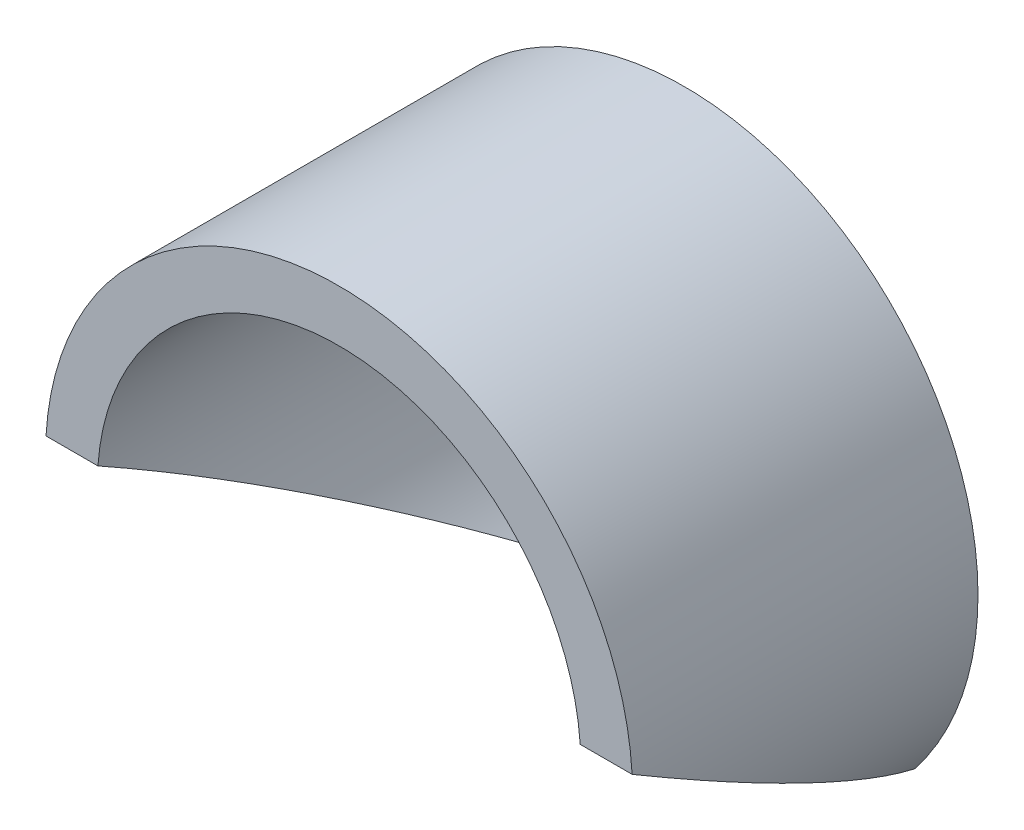
SolidWorks part; units mm, degrees
note: The reader was unsure of these and kept them because the rebuilt part matched: shared geometry of "Sketch23<2>".
ref_plane "Front Plane" through (0, 0, 0) normal (0, 0, 1) x (1, 0, 0)
ref_plane "Top Plane" through (0, 0, 0) normal (0, 1, 0) x (1, 0, 0)
ref_plane "Right Plane" through (0, 0, 0) normal (1, 0, 0) x (0, 0, -1)
sketch "Sketch1" plane through (0, 0, 0) normal (0, 1, 0) x (1, 0, 0)
  line L1 (0, 0) -> (121, 0)
  line L2 (0, 0) -> (0, -68)
  line L3 (0, -68) -> (121, -68)
  line L4 (121, 0) -> (121, -68)
  line L5 (5, -68) -> (116, -68)
  line L6 (5, -68) -> (5, -5)
  line L7 (5, -5) -> (116, -5)
  line L8 (116, -68) -> (116, -5)
  dimension "D1" = 121
  dimension "D2" = 68
  dimension "D3" = 5
  dimension "D4" = 5
  dimension "D5" = 5
extrude "Boss-Extrude1" add sketch "Sketch1" along normal blind 5 contours L8 L3 L4 L1 L2 L6 L7
ref_plane "Plane1" through (0, 3.75, 2.1651) normal (0, 0.866, 0.5) x (1, 0, 0)
sketch "Sketch2" plane through (0, 3.75, 2.1651) normal (0, 0.866, 0.5) x (1, 0, 0)
  line L2 (121, 2.5) -> (121, -56.3897) construction
  line L3 (0, 2.5) -> (121, 2.5) construction
  circle A0 centre (118.2001, -0.2999) radius 2.5
  dimension "D1" = 5
  dimension "D2" = 2.7999
  dimension "D3" = 2.7999
extrude "Boss-Extrude2" add sketch "Sketch2" along normal blind 100
ref_plane "Plane2" through (0, 0, 68) normal (0, 0, 1) x (1, 0, 0)
sketch "Sketch3" plane through (121, 0, 0) normal (1, 0, 0) x (0, 0, -1)
  line L0 (0, 5) -> (-68, 5) construction
  line L1 (0, 0) -> (-5, 0)
  line L2 (0, 0) -> (0, 5)
  line L3 (0, 5) -> (-5, 5)
  line L4 (-5, 0) -> (-5, 5)
  dimension "D1" = 5
extrude "Boss-Extrude3" add sketch "Sketch3" along normal blind 10
sketch "Sketch5" plane through (0, 3.75, 2.1651) normal (0, 0.866, 0.5) x (1, 0, 0)
  line L0 (131, -1.8301) -> (121, -1.8301) construction
  line L1 (131, 2.5) -> (126, 2.5)
  line L2 (131, 2.5) -> (131, -1.8301)
  line L3 (131, -1.8301) -> (126, -1.8301)
  line L4 (126, 2.5) -> (126, -1.8301)
  dimension "D1" = 5
extrude "Boss-Extrude4" add sketch "Sketch5" along normal offset from surface (117 mm away) 17 up to face at (118.2001, 88.9526, 54.5898) offset beyond the face yes
sketch "Sketch6" plane through (0, 1.25, -2.1651) normal (0, 0.5, -0.866) x (-1, 0, 0)
  line L0 (-126, 121.3301) -> (-126, 4.3301) construction
  line L1 (-131, 121.3301) -> (-126, 121.3301)
  line L2 (-131, 121.3301) -> (-131, 116.3301)
  line L3 (-131, 116.3301) -> (-126, 116.3301)
  line L4 (-126, 121.3301) -> (-126, 116.3301)
  dimension "D1" = 5
extrude "Boss-Extrude5" add sketch "Sketch6" along normal blind 20
sketch "Sketch7" plane through (126, 0, 0) normal (-1, 0, 0) x (0, 0, 1)
  line L0 (45.5096, 113.825) -> (41.1795, 116.325)
  line L1 (41.1795, 116.325) -> (62.25, 104.1599) construction
  line L2 (41.1795, 116.325) -> (38.6795, 111.9948)
  line L3 (38.6795, 111.9948) -> (43.0096, 109.4948)
  line L4 (38.6795, 111.9948) -> (56, 101.9948) construction
  line L5 (43.0096, 109.4948) -> (45.5096, 113.825)
  dimension "D1" = 90
  dimension "D2" = 5
extrude "Boss-Extrude6" add sketch "Sketch7" along normal blind 15
sketch "Sketch9" plane through (121, 0, 0) normal (1, 0, 0) x (0, 0, -1)
  line L0 (-62.25, 104.1599) -> (-62.25, 5) construction
  line L1 (-5, 5) -> (-68, 5) construction
  line L2 (-5, 0) -> (-68, 0) construction
  line L3 (-62.25, 5) -> (-57.25, 5)
  line L4 (-62.25, 5) -> (-62.25, 0)
  line L5 (-62.25, 0) -> (-57.25, 0)
  line L6 (-57.25, 5) -> (-57.25, 0)
  dimension "D1" = 5
extrude "Boss-Extrude7" add sketch "Sketch9" along normal up to surface (10 mm away) up to face at (131, 55.5593, 26.0136)
sketch "Sketch10" plane through (0, 5, 0) normal (0, 1, 0) x (1, 0, 0)
  line L0 (131, -57.25) -> (121, -57.25) construction
  line L1 (126, -57.25) -> (131, -57.25)
  line L2 (126, -57.25) -> (126, -62.25)
  line L3 (126, -62.25) -> (131, -62.25)
  line L4 (131, -57.25) -> (131, -62.25)
extrude "Boss-Extrude8" add sketch "Sketch10" along normal up to vertex
sketch "Sketch11" plane through (0, 0, 0) normal (-1, 0, 0) x (0, 0, 1)
  line L1 (62.25, 0) -> (52.25, 0)
  line L2 (62.25, 0) -> (62.25, 3)
  line L3 (62.25, 3) -> (52.25, 3)
  line L4 (52.25, 0) -> (52.25, 3)
  line L5 (0, 0) -> (10, 0)
  line L6 (0, 0) -> (0, 3)
  line L7 (0, 3) -> (10, 3)
  line L8 (10, 0) -> (10, 3)
  dimension "D1" = 10
  dimension "D2" = 3
  dimension "D3" = 10
  dimension "D4" = 3
extrude "Boss-Extrude9" add sketch "Sketch11" along normal blind 10
sketch "Sketch13" plane through (0, 3, 0) normal (0, 1, 0) x (1, 0, 0)
  line L0 (-5, -3) -> (-5, 0) construction
  line L1 (-10, 0) -> (0, 0) construction
  line L2 (-7, -5) -> (-10, -5) construction
  line L3 (-10, -10) -> (-10, 0) construction
  line L4 (-7, -57.25) -> (-10, -57.25) construction
  line L5 (-10, -62.25) -> (-10, -52.25) construction
  circle A0 centre (-5, -5) radius 2
  circle A1 centre (-5, -57.25) radius 2
  dimension "D1" = 4
extrude "Cut-Extrude1" cut sketch "Sketch13" against normal through all both and the other way through all
sketch "Sketch14" plane through (121, 0, 0) normal (1, 0, 0) x (0, 0, -1)
  line L0 (-5, 0) -> (-57.25, 0) construction
  line L1 (-20, 0) -> (-10, 0)
  line L2 (-20, 0) -> (-20, 3)
  line L3 (-20, 3) -> (-10, 3)
  line L4 (-10, 0) -> (-10, 3)
  line L5 (-57.25, 0) -> (-57.25, 5) construction
  line L6 (-42.25, 0) -> (-52.25, 0)
  line L7 (-42.25, 0) -> (-42.25, 3)
  line L8 (-42.25, 3) -> (-52.25, 3)
  line L9 (-52.25, 0) -> (-52.25, 3)
  line L10 (-5, 5) -> (-5, 0) construction
  dimension "D1" = 10
  dimension "D2" = 3
  dimension "D3" = 10
  dimension "D4" = 3
  dimension "D5" = 5
  dimension "D6" = 5
extrude "Boss-Extrude10" add sketch "Sketch14" along normal blind 20
sketch "Sketch15" plane through (0, 3, 0) normal (0, 1, 0) x (1, 0, 0)
  line L0 (138, -15) -> (141, -15) construction
  line L1 (141, -10) -> (141, -20) construction
  line L2 (136, -13) -> (136, -10) construction
  line L3 (141, -10) -> (121, -10) construction
  line L4 (136, -45.25) -> (136, -42.25) construction
  line L5 (141, -42.25) -> (121, -42.25) construction
  line L6 (138, -47.25) -> (141, -47.25) construction
  line L7 (141, -42.25) -> (141, -52.25) construction
  circle A0 centre (136, -15) radius 2
  circle A1 centre (136, -47.25) radius 2
  point P22 (141, -47.25)
  dimension "D1" = 4
extrude "Cut-Extrude2" cut sketch "Sketch15" against normal through all both and the other way through all
sketch "Sketch16" plane through (126, 0, 0) normal (-1, 0, 0) x (0, 0, 1)
  line L0 (49.8397, 111.325) -> (67, 101.4175)
  line L1 (49.8397, 111.325) -> (47.3397, 106.9948)
  line L2 (67, 101.4175) -> (64.5, 97.0874)
  line L3 (47.3397, 106.9948) -> (64.5, 97.0874)
  line L4 (45.5096, 113.825) -> (62.25, 104.1599) construction
  line L5 (43.0096, 109.4948) -> (56, 101.9948) construction
  line L6 (68, -54.223) -> (68, 54.223) construction
  line L7 (43.0096, 109.4948) -> (45.5096, 113.825) construction
  point P13 (44.2596, 111.6599)
  dimension "D1" = 1
  dimension "D2" = 90
  dimension "D3" = 5
extrude "Boss-Extrude11" add sketch "Sketch16" along normal blind 7.8
sketch "Sketch17" plane through (0, 105.075, 60.6651) normal (0, 0.866, 0.5) x (1, 0, 0)
  line L1 (131, 22.5) -> (108.821, 22.5)
  line L2 (131, 22.5) -> (131, 2.5)
  line L3 (131, 2.5) -> (108.821, 2.5)
  line L4 (108.821, 22.5) -> (108.821, 2.5)
  line L5 (0, 2.5) -> (126, 2.5) construction
extrude "Cut-Extrude3" cut sketch "Sketch17" against normal through all both and the other way through all
sketch "Sketch18" plane through (0, 0, 62.25) normal (0, 0, 1) x (1, 0, 0)
  line L0 (126, 104.1599) -> (118.2, 104.1599)
  line L1 (118.2, 104.1599) -> (102.2, 104.1599) construction
  line L2 (102.2, 104.1599) -> (100.7, 104.1599)
  arc A0 (102.2, 104.1599) -> (118.2, 104.1599) centre (110.2, 104.1599) cw
  arc A1 (100.7, 104.1599) -> (119.7, 104.1599) centre (110.2, 104.1599) cw
  dimension "D1" = 7.8
  dimension "D2" = 16
  dimension "D3" = 1.5
extrude "Boss-Extrude12" add sketch "Sketch18" along normal up to surface (5.75 mm away) and the other way blind 5 separate body contours A1 L2 A0 L0 up to plane "Plane2"
sketch "Sketch19" plane through (0, 104.1599, 0) normal (0, -1, 0) x (1, 0, 0)
  line L4 (119.7, 57.25) -> (119.7, 68)
  line L5 (119.7, 68) -> (118.2, 68)
  line L6 (118.2, 68) -> (118.2, 57.25)
  line L7 (118.2, 57.25) -> (119.7, 57.25)
  line L8 (119.7, 57.25) -> (119.7, 68)
  line L9 (119.7, 68) -> (118.2, 68)
  line L10 (118.2, 68) -> (118.2, 57.25)
  line L11 (118.2, 57.25) -> (119.7, 57.25)
  dimension "D1" = 0
extrude "Boss-Extrude13" add sketch "Sketch19" along normal up to vertex (2.7424 mm away) up to point (118.2, 101.4175, 67)
sketch "Sketch20" plane through (0, -3.6575, 6.3349) normal (0, -0.5, 0.866) x (1, 0, 0)
  line L5 (126, 116.3301) -> (126, 121.3301)
  line L6 (126, 121.3301) -> (119.7, 121.3301)
  line L7 (119.7, 121.3301) -> (118.2, 121.3301)
  line L8 (118.2, 121.3301) -> (118.2, 116.3301)
  line L9 (118.2, 116.3301) -> (126, 116.3301)
  line L10 (126, 116.3301) -> (126, 121.3301)
  line L11 (126, 121.3301) -> (119.7, 121.3301)
  line L12 (119.7, 121.3301) -> (118.2, 121.3301)
  line L13 (118.2, 121.3301) -> (118.2, 116.3301)
  line L14 (118.2, 116.3301) -> (126, 116.3301)
  dimension "D1" = 0
sketch "Sketch21" plane through (0, 101.4175, 0) normal (0, -1, 0) x (1, 0, 0)
  line L4 (118.2, 67) -> (119.7, 67)
  line L5 (119.7, 67) -> (119.7, 68)
  line L6 (119.7, 68) -> (118.2, 68)
  line L7 (118.2, 68) -> (118.2, 67)
  line L9 (119.7, 67) -> (119.7, 68)
  line L10 (119.7, 68) -> (118.2, 68)
  line L11 (118.2, 68) -> (118.2, 67)
  line L12 (118.2, 67) -> (119.7, 67)
  dimension "D1" = 0
extrude "Boss-Extrude15" add sketch "Sketch21" along normal blind 1
extrude "Boss-Extrude17" add sketch "Sketch20" against normal up to surface (1.1547 mm away)
ref_plane "Plane3" through (0, 104.1599, 0) normal (0, -1, 0) x (-1, 0, 0)
sketch "Sketch23" plane through (0, 104.1599, 0) normal (0, -1, 0) x (-1, 0, 0)
  line L1 (-126, -56) -> (-118.2, -56)
  line L2 (-126, -56) -> (-126, -68)
  line L3 (-126, -68) -> (-118.2, -68)
  line L4 (-118.2, -56) -> (-118.2, -68)
  dimension "D1" = 7.8
  dimension "D2" = 12
extrude "Cut-Extrude4" cut sketch "Sketch23" along normal blind 10 from offset 2
extrude "Boss-Extrude19" add sketch "Sketch23<2>" along normal blind 5 and the other way up to vertex (2.1651 mm away) other way up to point (119.45, 106.325, 58.5)
sketch "Sketch23<2>" plane through (0, 104.1599, 0) normal (0, -1, 0) x (-1, 0, 0) same geometry as "Sketch23"
sketch "Sketch24" plane through (0, 0, 56) normal (0, 0, -1) x (-1, 0, 0)
  line L5 (-126, 106.325) -> (-126, 101.9948)
  line L6 (-126, 101.9948) -> (-126, 99.1599)
  line L7 (-126, 99.1599) -> (-118.2, 99.1599)
  line L8 (-118.2, 99.1599) -> (-118.2, 106.325)
  line L9 (-118.2, 106.325) -> (-126, 106.325)
  line L10 (-126, 106.325) -> (-126, 101.9948)
  line L11 (-126, 101.9948) -> (-126, 99.1599)
  line L12 (-126, 99.1599) -> (-118.2, 99.1599)
  line L13 (-118.2, 99.1599) -> (-118.2, 106.325)
  line L14 (-118.2, 106.325) -> (-126, 106.325)
  dimension "D1" = 0
extrude "Cut-Extrude5" cut sketch "Sketch24" against normal up to surface (1.25 mm away) up to face at (111.5571, 108.2969, 57.25)
sketch "Sketch25" plane through (0, 105.075, 60.6651) normal (0, 0.866, 0.5) x (1, 0, 0)
  line L4 (126, 2.5) -> (126, -1.8301)
  line L5 (126, -1.8301) -> (131, -1.8301)
  line L6 (131, -1.8301) -> (131, 2.5)
  line L7 (131, 2.5) -> (126, 2.5)
  line L8 (126, 2.5) -> (126, -1.8301)
  line L9 (126, -1.8301) -> (131, -1.8301)
  line L10 (131, -1.8301) -> (131, 2.5)
  line L11 (131, 2.5) -> (126, 2.5)
  dimension "D1" = 0
extrude "Boss-Extrude20" add sketch "Sketch25" along normal up to surface (2.5 mm away) up to face at (123.38, 106.325, 61.8)
sketch "Sketch26" plane through (0, 0, 62.25) normal (0, 0, 1) x (1, 0, 0)
  line L1 (131, 104.1599) -> (126, 104.1599)
  line L2 (131, 104.1599) -> (131, 106.325)
  line L3 (131, 106.325) -> (126, 106.325)
  line L4 (126, 104.1599) -> (126, 106.325)
extrude "Cut-Extrude6" cut sketch "Sketch26" along normal blind 5
sketch "Sketch27" plane through (126, 0, 0) normal (1, 0, 0) x (0, 0, -1)
  line L4 (-62.25, 99.1599) -> (-62.25, 106.325)
  line L5 (-62.25, 106.325) -> (-68, 106.325)
  line L6 (-68, 106.325) -> (-68, 99.1599)
  line L7 (-68, 99.1599) -> (-62.25, 99.1599)
  line L8 (-62.25, 99.1599) -> (-62.25, 106.325)
  line L9 (-62.25, 106.325) -> (-68, 106.325)
  line L10 (-68, 106.325) -> (-68, 99.1599)
  line L11 (-68, 99.1599) -> (-62.25, 99.1599)
  dimension "D1" = 0
extrude "Boss-Extrude21" add sketch "Sketch27" along normal up to surface (5 mm away) up to face at (131, 35.35, 34.1667)
sketch "Sketch29" plane through (0, 0, 0) normal (-1, 0, 0) x (0, 0, 1)
  line L0 (26, 0) -> (26, 35) construction
  line L1 (10, 0) -> (52.25, 0) construction
  line L2 (0, 5) -> (0, 3) construction
  line L3 (0, 5) -> (68, 5) construction
  line L4 (38.5, 5) -> (38.5, 35)
  line L6 (38.5, 35) -> (41.5, 35)
  line L7 (38.5, 35) -> (38.5, 5)
  line L8 (38.5, 5) -> (41.5, 5)
  line L9 (41.5, 35) -> (41.5, 5)
  line M7 (68, 5) -> (0, 5)
  dimension "D1" = 30
  dimension "D2" = 26
  dimension "D3" = 35
  dimension "D4" = 12.5
  dimension "D5" = 12.5
  dimension "D6" = 3
extrude "Boss-Extrude22" add sketch "Sketch29" against normal blind 55 contours L9 L6 L4 M7
sketch "Sketch30" plane through (0, 5, 0) normal (0, -1, 0) x (1, 0, 0)
  line L0 (55, 41.5) -> (5, 41.5) construction
  line L1 (55, 38.5) -> (50, 38.5)
  line L2 (55, 38.5) -> (55, 41.5)
  line L3 (55, 41.5) -> (50, 41.5)
  line L4 (50, 38.5) -> (50, 41.5)
  dimension "D1" = 5
extrude "Boss-Extrude23" add sketch "Sketch30" along normal up to surface (5 mm away) up to face at (136, 0, 17)
sketch "Sketch31" plane through (0, 0, 38.5) normal (0, 0, -1) x (-1, 0, 0)
  line L0 (10, 0) -> (-131, 0) construction
  line L1 (-50, 5) -> (-55, 5)
  line L2 (-50, 5) -> (-50, 0)
  line L3 (-50, 0) -> (-55, 0)
  line L4 (-55, 5) -> (-55, 0)
  line L5 (-55, 0) -> (-55, 35) construction
extrude "Boss-Extrude24" add sketch "Sketch31" along normal up to surface (33.5 mm away) up to face at (60.5, 2.5, 5)
sketch "Sketch32" plane through (0, 0, 38.5) normal (0, 0, -1) x (-1, 0, 0)
  line L0 (-53, 9) -> (-41, 9)
  line L1 (-55, 35) -> (-55, 7)
  line L2 (-53, 35) -> (-57, 35)
  line L3 (-57, 35) -> (-57, 9)
  line L4 (-41, 7) -> (-69, 7)
  line L5 (-67, 35) -> (-67, 16)
  line L6 (-67, 35) -> (-69, 35)
  line L7 (-69, 35) -> (-69, 16)
  line L8 (-67, 16) -> (-69, 16)
  line L10 (-41, 7) -> (-41, 9)
  line L13 (-69, 7) -> (-69, 9)
  line L14 (-57, 9) -> (-69, 9)
  line L16 (-43, 16) -> (-41, 16)
  line L17 (-41, 35) -> (-41, 16)
  line L18 (-43, 35) -> (-41, 35)
  line L19 (-43, 35) -> (-43, 16)
  line L20 (-53, 35) -> (-53, 9)
  line M7 (0, 35) -> (-55, 35)
  line M8 (-55, 35) -> (-55, 5)
  dimension "D2" = 10
  dimension "D3" = 2
  dimension "D4" = 19
extrude "Boss-Extrude25" add sketch "Sketch32" along normal blind 12 contours L20 L4 L10 L0 M7 M8 | L19 L16 L17 M7
sketch "Sketch34" plane through (0, 35, 0) normal (0, 1, 0) x (1, 0, 0)
  line L1 (41, -38.5) -> (0, -38.5)
  line L2 (41, -38.5) -> (41, -41.5)
  line L3 (41, -41.5) -> (0, -41.5)
  line L4 (0, -38.5) -> (0, -41.5)
extrude "Cut-Extrude7" cut sketch "Sketch34" against normal up to surface (30 mm away) up to face at (118.2001, 5, 0.3463)
sketch "Sketch35" plane through (0, 7, 0) normal (0, -1, 0) x (1, 0, 0)
  line L4 (55, 38.5) -> (41, 38.5)
  line L5 (41, 38.5) -> (41, 26.5)
  line L6 (41, 26.5) -> (55, 26.5)
  line L7 (55, 26.5) -> (55, 38.5)
  line L8 (55, 38.5) -> (41, 38.5)
  line L9 (41, 38.5) -> (41, 26.5)
  line L10 (41, 26.5) -> (55, 26.5)
  line L11 (55, 26.5) -> (55, 38.5)
  dimension "D1" = 0
extrude "Boss-Extrude26" add sketch "Sketch35" along normal up to surface (7 mm away) up to face at (136, 0, 17)
sketch "Sketch36" plane through (0, 0, 38.5) normal (0, 0, 1) x (1, 0, 0)
  line L4 (50, 0) -> (50, 5)
  line L5 (50, 5) -> (41, 5)
  line L6 (41, 5) -> (41, 0)
  line L7 (41, 0) -> (50, 0)
  line L8 (50, 0) -> (50, 5)
  line L9 (50, 5) -> (41, 5)
  line L10 (41, 5) -> (41, 0)
  line L11 (41, 0) -> (50, 0)
  dimension "D1" = 0
extrude "Boss-Extrude27" add sketch "Sketch36" along normal up to surface and the other way up to surface up to face at (48.6667, 13.3333, 41.5) other way up to face at (27.5, 2.5, 5)
sketch "Sketch37" plane through (41, 0, 0) normal (-1, 0, 0) x (0, 0, 1)
  line L1 (41.5, 0) -> (0, 0)
  line L2 (41.5, 0) -> (41.5, 5)
  line L3 (41.5, 5) -> (0, 5)
  line L4 (0, 0) -> (0, 5)
extrude "Boss-Extrude28" add sketch "Sketch37" along normal up to surface (41 mm away) contours L2 L1 L4 L3 up to face at (0, 2.2, 38.5)
sketch "Sketch38" plane through (118.2, 0, 0) normal (-1, 0, 0) x (0, 0, 1)
  line L1 (44.0573, 123.2063) -> (78.3089, 123.2063)
  line L2 (44.0573, 123.2063) -> (44.0573, 96.1184)
  line L3 (44.0573, 96.1184) -> (78.3089, 96.1184)
  line L4 (78.3089, 123.2063) -> (78.3089, 96.1184)
extrude "Cut-Extrude8" cut sketch "Sketch38" along normal through all
sketch "Sketch39" plane through (0, 106.325, 0) normal (0, 1, 0) x (1, 0, 0)
  line L1 (86.6562, -42.2101) -> (154.3408, -42.2101)
  line L2 (86.6562, -42.2101) -> (86.6562, -72.2403)
  line L3 (86.6562, -72.2403) -> (154.3408, -72.2403)
  line L4 (154.3408, -42.2101) -> (154.3408, -72.2403)
extrude "Cut-Extrude9" cut sketch "Sketch39" along normal through all
sketch "Sketch42" plane through (0, 0, 68) normal (0, 0, 1) x (1, 0, 0)
  line L4 (131, 106.325) -> (118.2, 106.325)
  line L5 (118.2, 106.325) -> (118.2, 99.1599)
  line L6 (118.2, 99.1599) -> (131, 99.1599)
  line L7 (131, 99.1599) -> (131, 106.325)
  line L8 (131, 106.325) -> (118.2, 106.325)
  line L9 (118.2, 106.325) -> (118.2, 99.1599)
  line L10 (118.2, 99.1599) -> (131, 99.1599)
  line L11 (131, 99.1599) -> (131, 106.325)
  dimension "D1" = 0
sketch "Sketch43" plane through (0, 0, 57.25) normal (0, 0, -1) x (-1, 0, 0)
  line L0 (-120.7001, 90.2026) -> (-120.7001, 106.325) construction
  line L1 (-120.7001, 106.325) -> (-122.2001, 106.325) construction
  line L2 (-122.2001, 106.325) -> (-122.2001, 90.2026) construction
  line L3 (-122.2001, 90.2026) -> (-120.7001, 90.2026) construction
  line L4 (-118.2, 106.325) -> (-126, 106.325) construction
  line L5 (-120.7001, 106.325) -> (-104.7001, 106.325) construction
  line L6 (-104.7001, 106.325) -> (-103.7001, 106.325) construction
  line L7 (-104.7001, 106.325) -> (-104.7001, 90.2026) construction
  line L8 (-104.7001, 90.2026) -> (-103.7001, 90.2026) construction
  line L9 (-103.7001, 90.2026) -> (-103.7001, 106.325) construction
  line L10 (-122.2001, 106.325) -> (-126, 106.325)
  line L11 (-103.7001, 106.325) -> (-99.5874, 106.325)
  line L16 (-126, 106.325) -> (-126.3129, 106.325)
  arc A0 (-122.2001, 106.325) -> (-103.7001, 106.325) centre (-112.9501, 116.8339) cw
  arc A1 (-126.3129, 106.325) -> (-99.5874, 106.325) centre (-112.9501, 116.8339) cw
  arc A2 (-124.1823, 104.0731) -> (-101.718, 104.0731) centre (-112.9501, 116.8339) cw construction
  dimension "D4" = 14
  dimension "D1" = 1.5
  dimension "D2" = 16
  dimension "D3" = 1
  dimension "D5" = 3
sketch "Sketch44" plane through (118.2, 0, 0) normal (-1, 0, 0) x (0, 0, 1)
  line L1 (57.25, 106.325) -> (62.25, 106.325)
  line L2 (57.25, 106.325) -> (57.25, 99.1599)
  line L3 (57.25, 99.1599) -> (62.25, 99.1599)
  line L4 (62.25, 106.325) -> (62.25, 99.1599)
extrude "Boss-Extrude30" add sketch "Sketch44" along normal up to vertex (18.6126 mm away) up to point (99.5874, 106.325, 57.25)
extrude "Boss-Extrude31" add sketch "Sketch43" against normal blind 20
sketch "Sketch45" plane through (0, 0, 62.25) normal (0, 0, 1) x (1, 0, 0)
  line L5 (118.2, 99.1599) -> (118.2, 106.325)
  line L6 (118.2, 106.325) -> (103.7001, 106.325)
  line L7 (103.7001, 106.325) -> (99.5874, 106.325)
  line L8 (99.5874, 106.325) -> (99.5874, 99.1599)
  line L9 (99.5874, 99.1599) -> (118.2, 99.1599)
  line L10 (118.2, 99.1599) -> (118.2, 106.325)
  line L11 (118.2, 106.325) -> (103.7001, 106.325)
  line L12 (103.7001, 106.325) -> (99.5874, 106.325)
  line L13 (99.5874, 106.325) -> (99.5874, 99.1599)
  line L14 (99.5874, 99.1599) -> (118.2, 99.1599)
  dimension "D1" = 0
extrude "Boss-Extrude32" add sketch "Sketch45" along normal up to surface (15 mm away) up to face at (112.9501, 119.3294, 77.25)
sketch "Sketch46" plane through (0, 0, 62.25) normal (0, 0, 1) x (1, 0, 0)
  line L0 (126, 99.1599) -> (126, 5) construction
  line L1 (126, 89.1599) -> (131, 89.1599)
  line L2 (126, 89.1599) -> (126, 84.1599)
  line L3 (126, 84.1599) -> (131, 84.1599)
  line L4 (131, 89.1599) -> (131, 84.1599)
  line L5 (131, 99.1599) -> (131, 0) construction
  line L6 (118.2, 99.1599) -> (131, 99.1599) construction
  dimension "D1" = 5
  dimension "D2" = 10
extrude "EDIT THIS LENGTH" add sketch "Sketch46" along normal blind 50
sketch "Sketch47" plane through (0, 89.1599, 0) normal (0, 1, 0) x (1, 0, 0)
  line L0 (126, -112.25) -> (126, -62.25) construction
  line L1 (126, -109.25) -> (131, -109.25)
  line L2 (126, -109.25) -> (126, -112.25)
  line L3 (126, -112.25) -> (131, -112.25)
  line L4 (131, -109.25) -> (131, -112.25)
  dimension "D1" = 3
extrude "Boss-Extrude34" add sketch "Sketch47" along normal blind 5
sketch "Sketch53" plane through (0, 0, 57.25) normal (0, 0, -1) x (-1, 0, 0)
  line L0 (-103.7001, 106.325) -> (-99.5874, 106.325) construction
  line L1 (-205.1726, 106.325) -> (63.1762, 106.325)
  line L2 (-205.1726, 106.325) -> (-205.1726, -18.5333)
  line L3 (-205.1726, -18.5333) -> (63.1762, -18.5333)
  line L4 (63.1762, 106.325) -> (63.1762, -18.5333)
extrude "Cut-Extrude11" cut sketch "Sketch53" against normal through all both and the other way through all
chamfer "Chamfer1" distance 11.5 angle 60 2 edges at (124.2565, 106.325, 77.25) (101.6438, 106.325, 77.25) first distance on face at (112.9501, 119.3294, 77.25)
